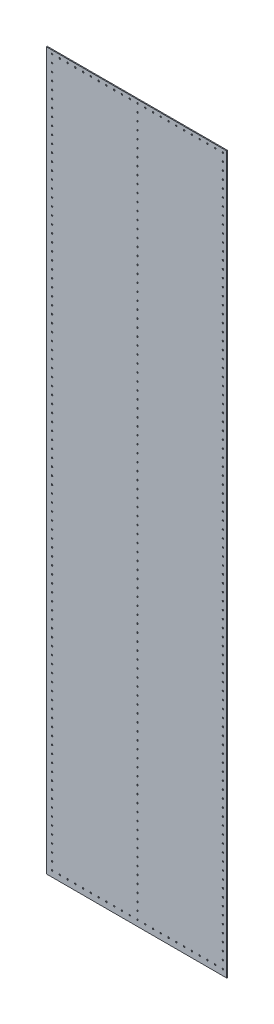
SolidWorks part; units mm, degrees
material "Ti-6Al-4VSolution treated and aged (SS)"
ref_plane "Front Plane" through (0, 0, 0) normal (0, 0, 1) x (1, 0, 0)
ref_plane "Top Plane" through (0, 0, 0) normal (0, 1, 0) x (1, 0, 0)
ref_plane "Right Plane" through (0, 0, 0) normal (1, 0, 0) x (0, 0, -1)
sketch "Sketch3" plane through (0, 0, 0) normal (0, 1, 0) x (1, 0, 0)
  line L0 (-578.87, 0) -> (578.87, 0)
  line L1 (578.87, 0) -> (580.6021, 3)
  line L2 (580.6021, 3) -> (-580.6021, 3)
  line L3 (0, 0) -> (0, 738.7484) construction
  line L5 (0, 3) -> (0, 0) construction
  line L6 (-578.87, 0) -> (-580.6021, 3)
  dimension "D1" = 578.87
  dimension "D2" = 120
  dimension "D3" = 3
extrude "Boss-Extrude1" add sketch "Sketch3" against normal blind 4613
chamfer "Chamfer1" distance 3 angle 45 1 edges at (0, 0, 0)
sketch "Sketch4" plane through (0, 0, -3) normal (0, 0, -1) x (-1, 0, 0)
  line L0 (-580.6021, 0) -> (580.6021, 0) construction
  line L1 (-580.6021, -4613) -> (-580.6021, 0) construction
  line L2 (-555.6021, -25) -> (-5.6021, -25) construction
  circle A0 centre (-555.6021, -25) radius 4.7625
  circle A1 centre (-505.6021, -25) radius 4.7625
  circle A2 centre (-455.6021, -25) radius 4.7625
  circle A3 centre (-405.6021, -25) radius 4.7625
  circle A4 centre (-355.6021, -25) radius 4.7625
  circle A5 centre (-305.6021, -25) radius 4.7625
  circle A6 centre (-255.6021, -25) radius 4.7625
  circle A7 centre (-205.6021, -25) radius 4.7625
  circle A8 centre (-155.6021, -25) radius 4.7625
  circle A9 centre (-105.6021, -25) radius 4.7625
  circle A10 centre (-55.6021, -25) radius 4.7625
  circle A11 centre (-5.6021, -25) radius 4.7625
  circle A12 centre (44.3979, -25) radius 4.7625
  circle A13 centre (94.3979, -25) radius 4.7625
  circle A14 centre (144.3979, -25) radius 4.7625
  circle A15 centre (194.3979, -25) radius 4.7625
  circle A16 centre (244.3979, -25) radius 4.7625
  circle A17 centre (294.3979, -25) radius 4.7625
  circle A18 centre (344.3979, -25) radius 4.7625
  circle A19 centre (394.3979, -25) radius 4.7625
  circle A20 centre (444.3979, -25) radius 4.7625
  circle A21 centre (494.3979, -25) radius 4.7625
  circle A22 centre (544.3979, -25) radius 4.7625
  circle A23 centre (-555.6021, -75) radius 4.7625
  circle A24 centre (-555.6021, -125) radius 4.7625
  circle A25 centre (-555.6021, -175) radius 4.7625
  circle A26 centre (-555.6021, -225) radius 4.7625
  circle A27 centre (-555.6021, -275) radius 4.7625
  circle A28 centre (-555.6021, -325) radius 4.7625
  circle A29 centre (-555.6021, -375) radius 4.7625
  circle A30 centre (-555.6021, -425) radius 4.7625
  circle A31 centre (-555.6021, -475) radius 4.7625
  circle A32 centre (-555.6021, -525) radius 4.7625
  circle A33 centre (-555.6021, -575) radius 4.7625
  circle A34 centre (-555.6021, -625) radius 4.7625
  circle A35 centre (-555.6021, -675) radius 4.7625
  circle A36 centre (-555.6021, -725) radius 4.7625
  circle A37 centre (-555.6021, -775) radius 4.7625
  circle A38 centre (-555.6021, -825) radius 4.7625
  circle A39 centre (-555.6021, -875) radius 4.7625
  circle A40 centre (-555.6021, -925) radius 4.7625
  circle A41 centre (-555.6021, -975) radius 4.7625
  circle A42 centre (-555.6021, -1025) radius 4.7625
  circle A43 centre (-555.6021, -1075) radius 4.7625
  circle A44 centre (-555.6021, -1125) radius 4.7625
  circle A45 centre (-555.6021, -1175) radius 4.7625
  circle A46 centre (-555.6021, -1225) radius 4.7625
  circle A47 centre (-555.6021, -1275) radius 4.7625
  circle A48 centre (-555.6021, -1325) radius 4.7625
  circle A49 centre (-555.6021, -1375) radius 4.7625
  circle A50 centre (-555.6021, -1425) radius 4.7625
  circle A51 centre (-555.6021, -1475) radius 4.7625
  circle A52 centre (-555.6021, -1525) radius 4.7625
  circle A53 centre (-555.6021, -1575) radius 4.7625
  circle A54 centre (-555.6021, -1625) radius 4.7625
  circle A55 centre (-555.6021, -1675) radius 4.7625
  circle A56 centre (-555.6021, -1725) radius 4.7625
  circle A57 centre (-555.6021, -1775) radius 4.7625
  circle A58 centre (-555.6021, -1825) radius 4.7625
  circle A59 centre (-555.6021, -1875) radius 4.7625
  circle A60 centre (-555.6021, -1925) radius 4.7625
  circle A61 centre (-555.6021, -1975) radius 4.7625
  circle A62 centre (-555.6021, -2025) radius 4.7625
  circle A63 centre (-555.6021, -2075) radius 4.7625
  circle A64 centre (-555.6021, -2125) radius 4.7625
  circle A65 centre (-555.6021, -2175) radius 4.7625
  circle A66 centre (-555.6021, -2225) radius 4.7625
  circle A67 centre (-555.6021, -2275) radius 4.7625
  circle A68 centre (-555.6021, -2325) radius 4.7625
  circle A69 centre (-555.6021, -2375) radius 4.7625
  circle A70 centre (-555.6021, -2425) radius 4.7625
  circle A71 centre (-555.6021, -2475) radius 4.7625
  circle A72 centre (-555.6021, -2525) radius 4.7625
  circle A73 centre (-555.6021, -2575) radius 4.7625
  circle A74 centre (-555.6021, -2625) radius 4.7625
  circle A75 centre (-555.6021, -2675) radius 4.7625
  circle A76 centre (-555.6021, -2725) radius 4.7625
  circle A77 centre (-555.6021, -2775) radius 4.7625
  circle A78 centre (-555.6021, -2825) radius 4.7625
  circle A79 centre (-555.6021, -2875) radius 4.7625
  circle A80 centre (-555.6021, -2925) radius 4.7625
  circle A81 centre (-555.6021, -2975) radius 4.7625
  circle A82 centre (-555.6021, -3025) radius 4.7625
  circle A83 centre (-555.6021, -3075) radius 4.7625
  circle A84 centre (-555.6021, -3125) radius 4.7625
  circle A85 centre (-555.6021, -3175) radius 4.7625
  circle A86 centre (-555.6021, -3225) radius 4.7625
  circle A87 centre (-555.6021, -3275) radius 4.7625
  circle A88 centre (-555.6021, -3325) radius 4.7625
  circle A89 centre (-555.6021, -3375) radius 4.7625
  circle A90 centre (-555.6021, -3425) radius 4.7625
  circle A91 centre (-555.6021, -3475) radius 4.7625
  circle A92 centre (-555.6021, -3525) radius 4.7625
  circle A93 centre (-555.6021, -3575) radius 4.7625
  circle A94 centre (-555.6021, -3625) radius 4.7625
  circle A95 centre (-555.6021, -3675) radius 4.7625
  circle A96 centre (-555.6021, -3725) radius 4.7625
  circle A97 centre (-555.6021, -3775) radius 4.7625
  circle A98 centre (-555.6021, -3825) radius 4.7625
  circle A99 centre (-555.6021, -3875) radius 4.7625
  circle A100 centre (-555.6021, -3925) radius 4.7625
  circle A101 centre (-555.6021, -3975) radius 4.7625
  circle A102 centre (-555.6021, -4025) radius 4.7625
  circle A103 centre (-555.6021, -4075) radius 4.7625
  circle A104 centre (-555.6021, -4125) radius 4.7625
  circle A105 centre (-555.6021, -4175) radius 4.7625
  circle A106 centre (-555.6021, -4225) radius 4.7625
  circle A107 centre (-555.6021, -4275) radius 4.7625
  circle A108 centre (-555.6021, -4325) radius 4.7625
  circle A109 centre (-555.6021, -4375) radius 4.7625
  circle A110 centre (-555.6021, -4425) radius 4.7625
  circle A111 centre (-555.6021, -4475) radius 4.7625
  circle A112 centre (-555.6021, -4525) radius 4.7625
  circle A113 centre (-555.6021, -4575) radius 4.7625
  circle A114 centre (-5.6021, -75) radius 4.7625
  circle A115 centre (-5.6021, -125) radius 4.7625
  circle A116 centre (-5.6021, -175) radius 4.7625
  circle A117 centre (-5.6021, -225) radius 4.7625
  circle A118 centre (-5.6021, -275) radius 4.7625
  circle A119 centre (-5.6021, -325) radius 4.7625
  circle A120 centre (-5.6021, -375) radius 4.7625
  circle A121 centre (-5.6021, -425) radius 4.7625
  circle A122 centre (-5.6021, -475) radius 4.7625
  circle A123 centre (-5.6021, -525) radius 4.7625
  circle A124 centre (-5.6021, -575) radius 4.7625
  circle A125 centre (-5.6021, -625) radius 4.7625
  circle A126 centre (-5.6021, -675) radius 4.7625
  circle A127 centre (-5.6021, -725) radius 4.7625
  circle A128 centre (-5.6021, -775) radius 4.7625
  circle A129 centre (-5.6021, -825) radius 4.7625
  circle A130 centre (-5.6021, -875) radius 4.7625
  circle A131 centre (-5.6021, -925) radius 4.7625
  circle A132 centre (-5.6021, -975) radius 4.7625
  circle A133 centre (-5.6021, -1025) radius 4.7625
  circle A134 centre (-5.6021, -1075) radius 4.7625
  circle A135 centre (-5.6021, -1125) radius 4.7625
  circle A136 centre (-5.6021, -1175) radius 4.7625
  circle A137 centre (-5.6021, -1225) radius 4.7625
  circle A138 centre (-5.6021, -1275) radius 4.7625
  circle A139 centre (-5.6021, -1325) radius 4.7625
  circle A140 centre (-5.6021, -1375) radius 4.7625
  circle A141 centre (-5.6021, -1425) radius 4.7625
  circle A142 centre (-5.6021, -1475) radius 4.7625
  circle A143 centre (-5.6021, -1525) radius 4.7625
  circle A144 centre (-5.6021, -1575) radius 4.7625
  circle A145 centre (-5.6021, -1625) radius 4.7625
  circle A146 centre (-5.6021, -1675) radius 4.7625
  circle A147 centre (-5.6021, -1725) radius 4.7625
  circle A148 centre (-5.6021, -1775) radius 4.7625
  circle A149 centre (-5.6021, -1825) radius 4.7625
  circle A150 centre (-5.6021, -1875) radius 4.7625
  circle A151 centre (-5.6021, -1925) radius 4.7625
  circle A152 centre (-5.6021, -1975) radius 4.7625
  circle A153 centre (-5.6021, -2025) radius 4.7625
  circle A154 centre (-5.6021, -2075) radius 4.7625
  circle A155 centre (-5.6021, -2125) radius 4.7625
  circle A156 centre (-5.6021, -2175) radius 4.7625
  circle A157 centre (-5.6021, -2225) radius 4.7625
  circle A158 centre (-5.6021, -2275) radius 4.7625
  circle A159 centre (-5.6021, -2325) radius 4.7625
  circle A160 centre (-5.6021, -2375) radius 4.7625
  circle A161 centre (-5.6021, -2425) radius 4.7625
  circle A162 centre (-5.6021, -2475) radius 4.7625
  circle A163 centre (-5.6021, -2525) radius 4.7625
  circle A164 centre (-5.6021, -2575) radius 4.7625
  circle A165 centre (-5.6021, -2625) radius 4.7625
  circle A166 centre (-5.6021, -2675) radius 4.7625
  circle A167 centre (-5.6021, -2725) radius 4.7625
  circle A168 centre (-5.6021, -2775) radius 4.7625
  circle A169 centre (-5.6021, -2825) radius 4.7625
  circle A170 centre (-5.6021, -2875) radius 4.7625
  circle A171 centre (-5.6021, -2925) radius 4.7625
  circle A172 centre (-5.6021, -2975) radius 4.7625
  circle A173 centre (-5.6021, -3025) radius 4.7625
  circle A174 centre (-5.6021, -3075) radius 4.7625
  circle A175 centre (-5.6021, -3125) radius 4.7625
  circle A176 centre (-5.6021, -3175) radius 4.7625
  circle A177 centre (-5.6021, -3225) radius 4.7625
  circle A178 centre (-5.6021, -3275) radius 4.7625
  circle A179 centre (-5.6021, -3325) radius 4.7625
  circle A180 centre (-5.6021, -3375) radius 4.7625
  circle A181 centre (-5.6021, -3425) radius 4.7625
  circle A182 centre (-5.6021, -3475) radius 4.7625
  circle A183 centre (-5.6021, -3525) radius 4.7625
  circle A184 centre (-5.6021, -3575) radius 4.7625
  circle A185 centre (-5.6021, -3625) radius 4.7625
  circle A186 centre (-5.6021, -3675) radius 4.7625
  circle A187 centre (-5.6021, -3725) radius 4.7625
  circle A188 centre (-5.6021, -3775) radius 4.7625
  circle A189 centre (-5.6021, -3825) radius 4.7625
  circle A190 centre (-5.6021, -3875) radius 4.7625
  circle A191 centre (-5.6021, -3925) radius 4.7625
  circle A192 centre (-5.6021, -3975) radius 4.7625
  circle A193 centre (-5.6021, -4025) radius 4.7625
  circle A194 centre (-5.6021, -4075) radius 4.7625
  circle A195 centre (-5.6021, -4125) radius 4.7625
  circle A196 centre (-5.6021, -4175) radius 4.7625
  circle A197 centre (-5.6021, -4225) radius 4.7625
  circle A198 centre (-5.6021, -4275) radius 4.7625
  circle A199 centre (-5.6021, -4325) radius 4.7625
  circle A200 centre (-5.6021, -4375) radius 4.7625
  circle A201 centre (-5.6021, -4425) radius 4.7625
  circle A202 centre (-5.6021, -4475) radius 4.7625
  circle A203 centre (-5.6021, -4525) radius 4.7625
  circle A204 centre (-5.6021, -4575) radius 4.7625
  circle A205 centre (544.3979, -75) radius 4.7625
  circle A206 centre (544.3979, -125) radius 4.7625
  circle A207 centre (544.3979, -175) radius 4.7625
  circle A208 centre (544.3979, -225) radius 4.7625
  circle A209 centre (544.3979, -275) radius 4.7625
  circle A210 centre (544.3979, -325) radius 4.7625
  circle A211 centre (544.3979, -375) radius 4.7625
  circle A212 centre (544.3979, -425) radius 4.7625
  circle A213 centre (544.3979, -475) radius 4.7625
  circle A214 centre (544.3979, -525) radius 4.7625
  circle A215 centre (544.3979, -575) radius 4.7625
  circle A216 centre (544.3979, -625) radius 4.7625
  circle A217 centre (544.3979, -675) radius 4.7625
  circle A218 centre (544.3979, -725) radius 4.7625
  circle A219 centre (544.3979, -775) radius 4.7625
  circle A220 centre (544.3979, -825) radius 4.7625
  circle A221 centre (544.3979, -875) radius 4.7625
  circle A222 centre (544.3979, -925) radius 4.7625
  circle A223 centre (544.3979, -975) radius 4.7625
  circle A224 centre (544.3979, -1025) radius 4.7625
  circle A225 centre (544.3979, -1075) radius 4.7625
  circle A226 centre (544.3979, -1125) radius 4.7625
  circle A227 centre (544.3979, -1175) radius 4.7625
  circle A228 centre (544.3979, -1225) radius 4.7625
  circle A229 centre (544.3979, -1275) radius 4.7625
  circle A230 centre (544.3979, -1325) radius 4.7625
  circle A231 centre (544.3979, -1375) radius 4.7625
  circle A232 centre (544.3979, -1425) radius 4.7625
  circle A233 centre (544.3979, -1475) radius 4.7625
  circle A234 centre (544.3979, -1525) radius 4.7625
  circle A235 centre (544.3979, -1575) radius 4.7625
  circle A236 centre (544.3979, -1625) radius 4.7625
  circle A237 centre (544.3979, -1675) radius 4.7625
  circle A238 centre (544.3979, -1725) radius 4.7625
  circle A239 centre (544.3979, -1775) radius 4.7625
  circle A240 centre (544.3979, -1825) radius 4.7625
  circle A241 centre (544.3979, -1875) radius 4.7625
  circle A242 centre (544.3979, -1925) radius 4.7625
  circle A243 centre (544.3979, -1975) radius 4.7625
  circle A244 centre (544.3979, -2025) radius 4.7625
  circle A245 centre (544.3979, -2075) radius 4.7625
  circle A246 centre (544.3979, -2125) radius 4.7625
  circle A247 centre (544.3979, -2175) radius 4.7625
  circle A248 centre (544.3979, -2225) radius 4.7625
  circle A249 centre (544.3979, -2275) radius 4.7625
  circle A250 centre (544.3979, -2325) radius 4.7625
  circle A251 centre (544.3979, -2375) radius 4.7625
  circle A252 centre (544.3979, -2425) radius 4.7625
  circle A253 centre (544.3979, -2475) radius 4.7625
  circle A254 centre (544.3979, -2525) radius 4.7625
  circle A255 centre (544.3979, -2575) radius 4.7625
  circle A256 centre (544.3979, -2625) radius 4.7625
  circle A257 centre (544.3979, -2675) radius 4.7625
  circle A258 centre (544.3979, -2725) radius 4.7625
  circle A259 centre (544.3979, -2775) radius 4.7625
  circle A260 centre (544.3979, -2825) radius 4.7625
  circle A261 centre (544.3979, -2875) radius 4.7625
  circle A262 centre (544.3979, -2925) radius 4.7625
  circle A263 centre (544.3979, -2975) radius 4.7625
  circle A264 centre (544.3979, -3025) radius 4.7625
  circle A265 centre (544.3979, -3075) radius 4.7625
  circle A266 centre (544.3979, -3125) radius 4.7625
  circle A267 centre (544.3979, -3175) radius 4.7625
  circle A268 centre (544.3979, -3225) radius 4.7625
  circle A269 centre (544.3979, -3275) radius 4.7625
  circle A270 centre (544.3979, -3325) radius 4.7625
  circle A271 centre (544.3979, -3375) radius 4.7625
  circle A272 centre (544.3979, -3425) radius 4.7625
  circle A273 centre (544.3979, -3475) radius 4.7625
  circle A274 centre (544.3979, -3525) radius 4.7625
  circle A275 centre (544.3979, -3575) radius 4.7625
  circle A276 centre (544.3979, -3625) radius 4.7625
  circle A277 centre (544.3979, -3675) radius 4.7625
  circle A278 centre (544.3979, -3725) radius 4.7625
  circle A279 centre (544.3979, -3775) radius 4.7625
  circle A280 centre (544.3979, -3825) radius 4.7625
  circle A281 centre (544.3979, -3875) radius 4.7625
  circle A282 centre (544.3979, -3925) radius 4.7625
  circle A283 centre (544.3979, -3975) radius 4.7625
  circle A284 centre (544.3979, -4025) radius 4.7625
  circle A285 centre (544.3979, -4075) radius 4.7625
  circle A286 centre (544.3979, -4125) radius 4.7625
  circle A287 centre (544.3979, -4175) radius 4.7625
  circle A288 centre (544.3979, -4225) radius 4.7625
  circle A289 centre (544.3979, -4275) radius 4.7625
  circle A290 centre (544.3979, -4325) radius 4.7625
  circle A291 centre (544.3979, -4375) radius 4.7625
  circle A292 centre (544.3979, -4425) radius 4.7625
  circle A293 centre (544.3979, -4475) radius 4.7625
  circle A294 centre (544.3979, -4525) radius 4.7625
  circle A295 centre (544.3979, -4575) radius 4.7625
  circle A296 centre (-5.6021, -25) radius 4.7625
  circle A297 centre (544.3979, -25) radius 4.7625
  circle A298 centre (-505.6021, -4575) radius 4.7625
  circle A299 centre (-455.6021, -4575) radius 4.7625
  circle A300 centre (-405.6021, -4575) radius 4.7625
  circle A301 centre (-355.6021, -4575) radius 4.7625
  circle A302 centre (-305.6021, -4575) radius 4.7625
  circle A303 centre (-255.6021, -4575) radius 4.7625
  circle A304 centre (-205.6021, -4575) radius 4.7625
  circle A305 centre (-155.6021, -4575) radius 4.7625
  circle A306 centre (-105.6021, -4575) radius 4.7625
  circle A307 centre (-55.6021, -4575) radius 4.7625
  circle A308 centre (-5.6021, -4575) radius 4.7625
  circle A309 centre (44.3979, -4575) radius 4.7625
  circle A310 centre (94.3979, -4575) radius 4.7625
  circle A311 centre (144.3979, -4575) radius 4.7625
  circle A312 centre (194.3979, -4575) radius 4.7625
  circle A313 centre (244.3979, -4575) radius 4.7625
  circle A314 centre (294.3979, -4575) radius 4.7625
  circle A315 centre (344.3979, -4575) radius 4.7625
  circle A316 centre (394.3979, -4575) radius 4.7625
  circle A317 centre (444.3979, -4575) radius 4.7625
  circle A318 centre (494.3979, -4575) radius 4.7625
  circle A319 centre (544.3979, -4575) radius 4.7625
  dimension "D3" = 9.525
  dimension "D1" = 25
  dimension "D2" = 25
  dimension "D7" = 550
  dimension "D4" = 23
  dimension "D5" = 92
  dimension "D6" = 3
  dimension "D8" = 23
extrude "Cut-Extrude1" cut sketch "Sketch4" along direction (0, 0, -1) on the side against the normal through all
